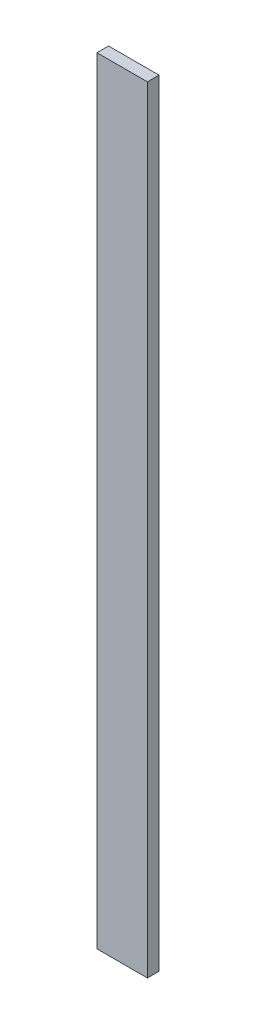
SolidWorks part; units mm, degrees
ref_plane "Front Plane" through (0, 0, 0) normal (0, 0, 1) x (1, 0, 0)
ref_plane "Top Plane" through (0, 0, 0) normal (0, 1, 0) x (1, 0, 0)
ref_plane "Right Plane" through (0, 0, 0) normal (1, 0, 0) x (0, 0, -1)
sketch "Sketch1" plane through (0, 0, 0) normal (0, 1, 0) x (1, 0, 0)
  line L1 (-97.5, 22.5) -> (97.5, 22.5)
  line L2 (-97.5, 22.5) -> (-97.5, -22.5)
  line L3 (-97.5, -22.5) -> (97.5, -22.5)
  line L4 (97.5, 22.5) -> (97.5, -22.5)
  line L5 (-97.5, 22.5) -> (97.5, -22.5) construction
  line L6 (-97.5, -22.5) -> (97.5, 22.5) construction
  point P0 (0, 0)
  dimension "D1" = 45
  dimension "D2" = 195
extrude "Shape" add sketch "Sketch1" along normal blind 3000
